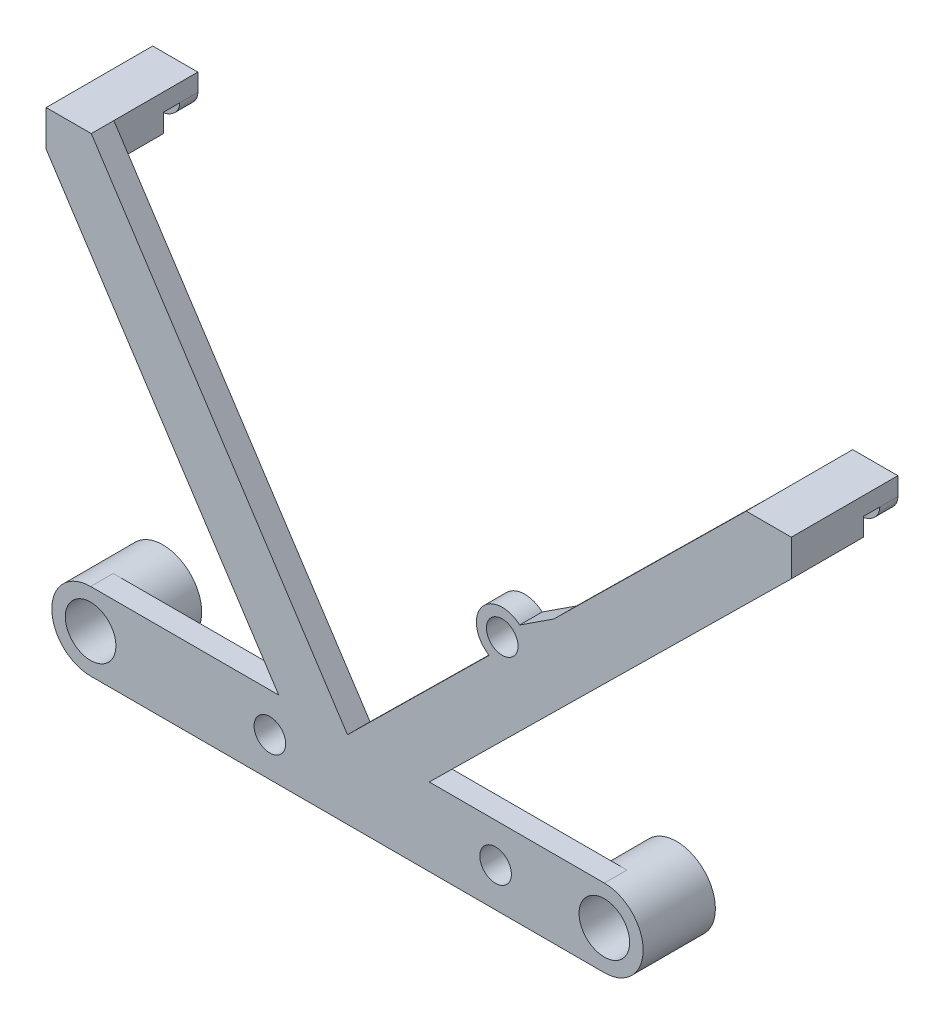
SolidWorks part; units mm, degrees
ref_plane "Front Plane" through (0, 0, 0) normal (0, 0, 1) x (1, 0, 0)
ref_plane "Top Plane" through (0, 0, 0) normal (0, 1, 0) x (1, 0, 0)
ref_plane "Right Plane" through (0, 0, 0) normal (1, 0, 0) x (0, 0, -1)
sketch "Sketch1" plane through (0, 0, 0) normal (0, 0, 1) x (1, 0, 0)
  line L0 (-0.2008, 50.5421) -> (-101.0291, 50.5421) construction
  line L1 (-23.6983, 50.5421) -> (-18.6983, 50.5421)
  line L2 (-23.6983, 50.5421) -> (-23.6983, 48.5421)
  line L3 (-23.6983, 48.5421) -> (-18.6983, 48.5421)
  line L4 (-18.6983, 50.5421) -> (-18.6983, 48.5421)
  line L6 (-23.6983, 50.5421) -> (-18.6983, 50.5421)
  line L7 (-23.6983, 50.5421) -> (-23.6983, 52.5421)
  line L8 (-23.6983, 52.5421) -> (-18.6983, 52.5421)
  line L9 (-18.6983, 50.5421) -> (-18.6983, 52.5421)
  line L10 (-101.2299, 50.488) -> (-96.2299, 50.488)
  line L11 (-101.2299, 50.488) -> (-101.2299, 48.488)
  line L12 (-101.2299, 48.488) -> (-96.2299, 48.488)
  line L13 (-96.2299, 50.488) -> (-96.2299, 48.488)
  line L14 (-96.2299, 50.488) -> (-101.2299, 50.488)
  line L15 (-96.2299, 50.488) -> (-96.2299, 52.488)
  line L16 (-96.2299, 52.488) -> (-101.2299, 52.488)
  line L17 (-101.2299, 50.488) -> (-101.2299, 52.488)
  circle A1 centre (-39.408, 4.712) radius 2.2
  circle A2 centre (-96.304, 4.712) radius 2.2
  circle A3 centre (-39.408, 4.712) radius 2.8
  circle A4 centre (-39.408, 4.712) radius 4.3
  circle A5 centre (-96.304, 4.712) radius 2.8
  circle A6 centre (-96.304, 4.712) radius 4.3
  dimension "D5" = 5.6
  dimension "D6" = 8.6
  dimension "D7" = 8.6
  dimension "D8" = 5.6
  dimension "D1" = 2
  dimension "D2" = 2
  dimension "D3" = 2
  dimension "D4" = 2
  dimension "D9" = 5
  dimension "D10" = 5
extrude "Boss-Extrude1" add sketch "Sketch1" along normal blind 5.5 contours A6 A5 | A4 A3 | L13 L10 L11 L12 | L17 L10 L15 L16 | L4 L1 L2 L3 | L1 L9 L8 L7 region at (-21.1983, 51.5421, 0) region at (-21.1983, 49.5421, 0) region at (-98.7299, 51.488, 0) region at (-98.7299, 49.488, 0) region at (-43.5864, 4.712, 0) region at (-100.4824, 4.712, 0)
sketch "Sketch2" plane through (0, 0, 5.5) normal (0, 0, 1) x (1, 0, 0)
  line L0 (-96.304, 4.712) -> (-39.408, 4.712) construction
  line L1 (-96.304, 9.012) -> (-39.408, 9.012)
  line L2 (-96.304, 0.412) -> (-39.408, 0.412)
  line L3 (-67.856, 4.712) -> (-67.856, 9.012)
  line L4 (-67.856, 9.012) -> (-67.856, 4.712)
  line L5 (-67.856, 0.412) -> (-67.856, 4.712)
  line L6 (-67.856, 9.012) -> (-96.2299, 52.488)
  line L7 (-96.2299, 52.488) -> (-101.2299, 52.488)
  line L8 (-101.2299, 52.488) -> (-101.2299, 48.488)
  line L9 (-101.2299, 48.488) -> (-69.8539, 0.412)
  line L10 (-67.856, 9.012) -> (-23.6983, 52.5421)
  line L11 (-23.6983, 52.5421) -> (-18.6983, 52.5421)
  line L12 (-18.6983, 52.5421) -> (-18.6983, 48.5421)
  line L13 (-18.6983, 48.5421) -> (-67.5223, 0.412)
  arc A0 (-96.304, 9.012) -> (-96.304, 0.412) centre (-96.304, 4.712) ccw
  arc A1 (-39.408, 0.412) -> (-39.408, 9.012) centre (-39.408, 4.712) ccw
  circle A2 centre (-39.408, 4.712) radius 2.8
  circle A3 centre (-96.304, 4.712) radius 2.8
  point P4 (-67.856, 4.712)
  circle M3 centre (-96.304, 4.712) radius 2.8
  circle M4 centre (-96.304, 4.712) radius 4.3
  dimension "D1" = 8.6
extrude "Boss-Extrude2" add sketch "Sketch2" along normal blind 2.5 contours L2 A1 L1 L13 A2 | L0 L9 L1 M4 | L0 L2 L9 M4 | M3 M4 | L3 L0 L13 L1 | L9 L0 L3 L1 | L0 L9 L2 L5 | L0 L5 L2 L13 | L13 L12 L11 L10 L1 | L8 L9 L1 L6 L7 region at (-93.3494, 1.7574, 5.5) region at (-83.5021, 6.8669, 5.5) region at (-82.098, 2.4649, 5.5) region at (-71.0125, 7.024, 5.5) region at (-69.653, 2.8577, 5.5) region at (-64.3024, 7.0893, 5.5) region at (-66.2834, 3.1836, 5.5) region at (-85.5876, 30.4228, 5.5) region at (-50.9097, 4.4543, 5.5) region at (-41.7506, 30.3477, 5.5)
sketch "Sketch3" plane through (0, 0, 0) normal (0, 0, -1) x (-1, 0, 0)
  line L0 (23.6983, 52.5421) -> (23.6983, 48.5421) construction
  line L1 (18.6983, 52.5421) -> (23.6983, 52.5421)
  line L2 (18.6983, 52.5421) -> (18.6983, 50.5421)
  line L3 (18.6983, 50.5421) -> (23.6983, 50.5421)
  line L4 (23.6983, 52.5421) -> (23.6983, 50.5421)
  line L5 (96.2299, 52.488) -> (96.2299, 48.488) construction
  line L6 (101.2299, 52.488) -> (96.2299, 52.488)
  line L7 (101.2299, 52.488) -> (101.2299, 50.5421)
  line L8 (101.2299, 50.5421) -> (96.2299, 50.5421)
  line L9 (96.2299, 52.488) -> (96.2299, 50.5421)
  line L10 (0.2008, 50.5421) -> (101.0291, 50.5421) construction
extrude "Boss-Extrude3" add sketch "Sketch3" along normal blind 1.8
sketch "Sketch4" plane through (0, 0, -1.8) normal (0, 0, -1) x (-1, 0, 0)
  line L0 (18.6983, 50.5421) -> (23.6983, 50.5421) construction
  line L1 (96.2299, 50.5421) -> (101.2299, 50.5421) construction
  line L2 (18.6983, 50.5421) -> (18.6983, 52.5421)
  line L3 (18.6983, 52.5421) -> (23.6983, 52.5421)
  line L4 (23.6983, 52.5421) -> (23.6983, 50.5421)
  line L5 (96.2299, 50.5421) -> (96.2299, 52.488)
  line L6 (96.2299, 52.488) -> (101.2299, 52.488)
  line L7 (101.2299, 52.488) -> (101.2299, 50.5421)
  ellipse E0 centre (21.1983, 50.5421) end of major axis (23.6983, 50.5421) minor radius 2
  ellipse E1 centre (98.7299, 50.5421) end of major axis (101.2299, 50.5421) minor radius 1.9459
  line M3 (18.6983, 52.5421) -> (18.6983, 50.5421)
  line M4 (18.6983, 50.5421) -> (23.6983, 50.5421)
  line M5 (23.6983, 50.5421) -> (23.6983, 52.5421)
  line M6 (23.6983, 52.5421) -> (18.6983, 52.5421)
extrude "Boss-Extrude4" add sketch "Sketch4" along normal blind 2 contours E1 L7 L6 | E1 L6 L5 | E1 | E0 L3 M3 | E0 M5 M6 | E0 M4 | E0 M4 region at (-21.1983, 49.6933, -1.8) region at (-19.2567, 52.0953, -1.8) region at (-21.1983, 51.3909, -1.8) region at (-23.1399, 52.0953, -1.8) region at (-98.7299, 50.5421, -1.8) region at (-96.7883, 52.0533, -1.8) region at (-100.6715, 52.0533, -1.8)
sketch "Sketch5" plane through (0, 0, 8) normal (0, 0, 1) x (1, 0, 0)
  line L0 (-39.408, 4.712) -> (-96.304, 4.712)
  circle A0 centre (-36.4512, 4.712) radius 1.75
  circle A1 centre (-76.4512, 4.712) radius 1.75
  dimension "D2" = 3.5
  dimension "D3" = 3.5
  dimension "D1" = 40
extrude "Cut-Extrude1" cut sketch "Sketch5" against normal up to next contours L0 A1 | L0 A1 region at (-76.4512, 3.9693, 8) region at (-76.4512, 5.4547, 8)
sketch "Sketch6" plane through (0, 0, 5.5) normal (0, 0, -1) x (-1, 0, 0)
  line L0 (52.5786, 24.7808) -> (52.1941, 24.4513)
  line L1 (67.856, 9.012) -> (23.6983, 52.5421) construction
  line L2 (48.7929, 29.0699) -> (45.0004, 31.5428)
  line L3 (45.0004, 31.5428) -> (52.1941, 24.4513)
  circle A0 centre (50.7168, 26.9528) radius 1.75
  arc A1 (48.7929, 29.0699) -> (52.5786, 24.7808) centre (50.7168, 26.9528) cw
  line M18 (67.856, 9.012) -> (23.6983, 52.5421)
  dimension "D1" = 3.5
extrude "Boss-Extrude5" add sketch "Sketch6" against normal through all contours A1 L2 A0 L0 M18 region at (-52.3139, 24.7005, 5.5)
sketch "Sketch7" plane through (0, 0, 5.5) normal (0, 0, -1) x (-1, 0, 0)
  line L0 (76.4512, 4.712) -> (51.4512, 4.712)
  circle A0 centre (51.4512, 4.712) radius 1.75
  dimension "D1" = 3.5
  dimension "D2" = 25
extrude "Cut-Extrude2" cut sketch "Sketch7" against normal through all contours A0 region at (-49.7507, 4.712, 5.5)
extrude "Cut-Extrude3" cut sketch "Sketch6<3>" against normal blind 12.446 contours L3 A0 region at (-49.9035, 26.1277, 5.5)
sketch "Sketch6<3>" plane through (0, 0, 5.5) normal (0, 0, -1) x (-1, 0, 0) same geometry as "Sketch6"
